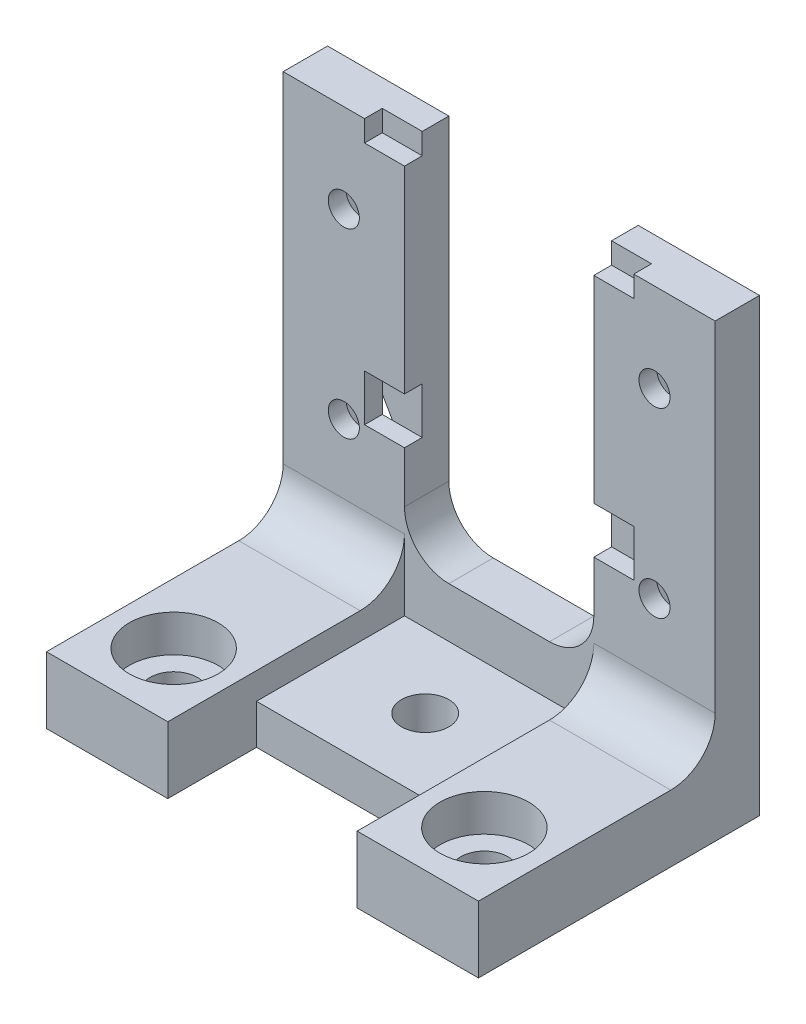
SolidWorks part; units mm, degrees
ref_plane "Plano frontal" through (0, 0, 0) normal (0, 0, 1) x (1, 0, 0)
ref_plane "Plano superior" through (0, 0, 0) normal (0, 1, 0) x (1, 0, 0)
ref_plane "Plano direito" through (0, 0, 0) normal (1, 0, 0) x (0, 0, -1)
sketch "Esboço2" plane through (0, 0, -1) normal (0, 0, -1) x (-1, 0, 0)
  line L1 (14.6, 8.1) -> (6.4, 8.1)
  line L2 (14.6, 8.1) -> (14.6, -22.3604)
  line L3 (14.6, -22.3604) -> (6.4, -22.3604)
  line L4 (6.4, 8.1) -> (6.4, -22.3604)
  line L5 (6.4, 8.1) -> (-21.6025, 8.1) construction
  line L6 (-12.6, -12) -> (-12.6, 12) construction
  line L7 (-14.6, 8.1) -> (-6.4, 8.1)
  line L8 (-14.6, 8.1) -> (-14.6, -22.3604)
  line L9 (-14.6, -22.3604) -> (-6.4, -22.3604)
  line L10 (-6.4, 8.1) -> (-6.4, -22.3604)
  line L11 (12.6, -12) -> (12.6, 12) construction
  line L12 (-4.4, -2.7) -> (-4.4, 6.1) construction
  circle A0 centre (-10.5, 2.1) radius 1.05 construction
  dimension "D3" = 6
  dimension "D1" = 2
  dimension "D2" = 2
  dimension "D4" = 2
extrude "Ressalto-extrusão1" add sketch "Esboço2" along normal blind 3
sketch "Esboço3" plane through (-6.4, 0, 0) normal (1, 0, 0) x (0, 0, -1)
  line L0 (4, 8.1) -> (4, -22.3604) construction
  line L1 (1, -22.3604) -> (4, -22.3604)
  line L2 (1, -22.3604) -> (1, -16.2722)
  line L3 (1, -16.2722) -> (4, -16.2722)
  line L4 (4, -22.3604) -> (4, -16.2722)
extrude "Ressalto-extrusão2" add sketch "Esboço3" along normal up to next
sketch "Esboço4" plane through (0, 0, -1) normal (0, 0, 1) x (1, 0, 0)
  line L0 (14.6, -22.3604) -> (-14.6, -22.3604) construction
  line L1 (-6.4, -22.3604) -> (6.4, -22.3604)
  line L2 (-6.4, -22.3604) -> (-6.4, -19.6604)
  line L3 (-6.4, -19.6604) -> (6.4, -19.6604)
  line L4 (6.4, -22.3604) -> (6.4, -19.6604)
  line L5 (6.4, -16.2722) -> (6.4, 8.1) construction
  line L6 (-6.4, 8.1) -> (-6.4, -16.2722) construction
  dimension "D1" = 2.7
extrude "Ressalto-extrusão3" add sketch "Esboço4" along normal blind 10
sketch "Esboço5" plane through (0, 0, -1) normal (0, 0, 1) x (1, 0, 0)
  line L0 (14.6, 8.1) -> (14.6, -22.3604) construction
  line L1 (-14.6, -22.3604) -> (-6.4, -22.3604)
  line L2 (-14.6, -22.3604) -> (-14.6, -17.8604)
  line L3 (-14.6, -17.8604) -> (-6.4, -17.8604)
  line L4 (-6.4, -22.3604) -> (-6.4, -17.8604)
  line L5 (6.4, -22.3604) -> (14.6, -22.3604)
  line L6 (6.4, -22.3604) -> (6.4, -17.8604)
  line L7 (6.4, -17.8604) -> (14.6, -17.8604)
  line L8 (14.6, -22.3604) -> (14.6, -17.8604)
  line L9 (-6.4, -19.6604) -> (-6.4, -22.3604) construction
  dimension "D1" = 4.5
extrude "Ressalto-extrusão4" add sketch "Esboço5" along normal blind 16
sketch "Esboço6" plane through (0, -17.8604, 0) normal (0, 1, 0) x (1, 0, 0)
  line L0 (6.4, -9) -> (-6.4, 1) construction
  line L1 (6.4, -15) -> (6.4, 1) construction
  line L2 (-14.6, -10.5) -> (-6.4, -10.5) construction
  line L3 (-14.6, -15) -> (-14.6, 1) construction
  line L4 (-6.4, -15) -> (-6.4, 1) construction
  line L5 (-6.4, -10.5) -> (6.4, -10.5) construction
  line L6 (6.4, -10.5) -> (14.6, -10.5) construction
  line L7 (14.6, -15) -> (14.6, 1) construction
  line L8 (14.6, -15) -> (6.4, -15) construction
  circle A0 centre (0, -4) radius 1.6
  circle A1 centre (10.5, -10.5) radius 1.6
  circle A2 centre (-10.5, -10.5) radius 1.6
  dimension "D1" = 3.2
  dimension "D2" = 4.5
extrude "Corte-extrusão1" cut sketch "Esboço6" against normal through all both and the other way through all
sketch "Esboço7" plane through (0, -17.8604, 0) normal (0, 1, 0) x (1, 0, 0)
  circle A0 centre (10.5, -10.5) radius 3
  circle A1 centre (-10.5, -10.5) radius 3
  dimension "D1" = 6
extrude "Corte-extrusão2" cut sketch "Esboço7" against normal blind 2.5
sketch "Esboço8" plane through (0, 0, -1) normal (0, 0, 1) x (1, 0, 0)
  circle A0 centre (-10.5, 2.1) radius 1.05
  circle A1 centre (10.5, 2.1) radius 1.05
  circle A2 centre (10.5, -10.2) radius 1.05
  circle A3 centre (-10.5, -10.2) radius 1.05
  dimension "D1" = 2.1
extrude "Corte-extrusão3" cut sketch "Esboço8" against normal through all
fillet "Filete1" radius 3 2 edges at (6.4, -16.2722, -2.5) (-6.4, -16.2722, -2.5)
sketch "Esboço9" plane through (6.4, 0, 0) normal (-1, 0, 0) x (0, 0, 1)
  line L0 (-1, -13.2722) -> (-1, 8.1) construction
  line L1 (-1, -6.6712) -> (-2.2, -6.6712)
  line L2 (-1, -6.6712) -> (-1, -9.82)
  line L3 (-1, -9.82) -> (-2.2, -9.82)
  line L4 (-2.2, -6.6712) -> (-2.2, -9.82)
extrude "Corte-extrusão4" cut sketch "Esboço9" against normal blind 2.7
fillet "Filete2" radius 3 2 edges at (10.5, -17.8604, -1) (-10.5, -17.8604, -1)
sketch "Esboço10" plane through (0, 0, -4) normal (0, 0, -1) x (-1, 0, 0)
  line L0 (0, -16.2722) -> (0, 4.5459) construction
  line L1 (12.8094, 2.1) -> (11.6547, 4.1)
  line L2 (11.6547, 4.1) -> (9.3453, 4.1)
  line L3 (9.3453, 4.1) -> (8.1906, 2.1)
  line L4 (8.1906, 2.1) -> (9.3453, 0.1)
  line L5 (9.3453, 0.1) -> (11.6547, 0.1)
  line L6 (11.6547, 0.1) -> (12.8094, 2.1)
  line L7 (12.8094, -10.2) -> (11.6547, -8.2)
  line L8 (11.6547, -8.2) -> (9.3453, -8.2)
  line L9 (9.3453, -8.2) -> (8.1906, -10.2)
  line L10 (8.1906, -10.2) -> (9.3453, -12.2)
  line L11 (9.3453, -12.2) -> (11.6547, -12.2)
  line L12 (11.6547, -12.2) -> (12.8094, -10.2)
  line L13 (-3.4, -16.2722) -> (3.4, -16.2722) construction
  line L14 (-11.6547, -12.2) -> (-12.8094, -10.2)
  line L15 (-9.3453, -12.2) -> (-11.6547, -12.2)
  line L16 (-8.1906, -10.2) -> (-9.3453, -12.2)
  line L17 (-9.3453, -8.2) -> (-8.1906, -10.2)
  line L18 (-11.6547, -8.2) -> (-9.3453, -8.2)
  line L19 (-12.8094, -10.2) -> (-11.6547, -8.2)
  line L20 (-11.6547, 0.1) -> (-12.8094, 2.1)
  line L21 (-9.3453, 0.1) -> (-11.6547, 0.1)
  line L22 (-8.1906, 2.1) -> (-9.3453, 0.1)
  line L23 (-9.3453, 4.1) -> (-8.1906, 2.1)
  line L24 (-11.6547, 4.1) -> (-9.3453, 4.1)
  line L25 (-12.8094, 2.1) -> (-11.6547, 4.1)
  circle A0 centre (10.5, 2.1) radius 2 construction
  circle A1 centre (10.5, -10.2) radius 2 construction
  circle A2 centre (-10.5, -10.2) radius 2 construction
  circle A3 centre (-10.5, 2.1) radius 2 construction
  point P25 (10.5, 0.1)
  dimension "D1" = 4
extrude "Corte-extrusão5" cut sketch "Esboço10" against normal blind 1.8
sketch "Esboço11" plane through (0, -17.8604, 0) normal (0, 1, 0) x (1, 0, 0)
  line L0 (0, 0) -> (0, -34) construction
  line L1 (8.25, -11) -> (-8.25, -11)
  line L2 (8.25, -11) -> (8.25, -17)
  line L3 (8.25, -17) -> (-8.25, -17)
  line L4 (-8.25, -11) -> (-8.25, -17)
  line L5 (6.4, -9) -> (-6.4, -9) construction
  point P7 (0, -17)
  dimension "D1" = 16.5
  dimension "D2" = 6
  dimension "D3" = 2
sketch "Esboço13" plane through (0, 0, -1) normal (0, 0, 1) x (1, 0, 0)
  line L0 (12.6426, 0) -> (0, 0) construction
  line L1 (12.6426, 12) -> (12.6426, -12) construction
  line L2 (9.1, -6.6712) -> (6.4, -6.6712) construction
  line L3 (6.4, -6.6712) -> (6.4, -9.82) construction
  line L4 (9.1, -9.82) -> (6.4, -9.82) construction
  line L5 (9.1, -9.82) -> (9.1, -6.6712) construction
  line L6 (9.1, -6.6712) -> (6.4, -6.6712)
  line L7 (6.4, -6.6712) -> (6.4, -9.82)
  line L8 (9.1, -9.82) -> (6.4, -9.82)
  line L9 (9.1, -9.82) -> (9.1, -6.6712)
  line L10 (0, 0) -> (0, -9.82) construction
  line L11 (9.1, 9.82) -> (9.1, 6.6712)
  line L12 (9.1, 9.82) -> (6.4, 9.82)
  line L13 (6.4, 6.6712) -> (6.4, 9.82)
  line L14 (9.1, 6.6712) -> (6.4, 6.6712)
  line L15 (-9.1, 6.6712) -> (-6.4, 6.6712)
  line L16 (-6.4, 6.6712) -> (-6.4, 9.82)
  line L17 (-9.1, 9.82) -> (-6.4, 9.82)
  line L18 (-9.1, 9.82) -> (-9.1, 6.6712)
  line L19 (-9.1, -9.82) -> (-9.1, -6.6712)
  line L20 (-9.1, -9.82) -> (-6.4, -9.82)
  line L21 (-6.4, -6.6712) -> (-6.4, -9.82)
  line L22 (-9.1, -6.6712) -> (-6.4, -6.6712)
extrude "Corte-extrusão7" cut sketch "Esboço13" against normal up to surface (1.2 mm away) up to face at (7.882, -8.3215, -2.2)
